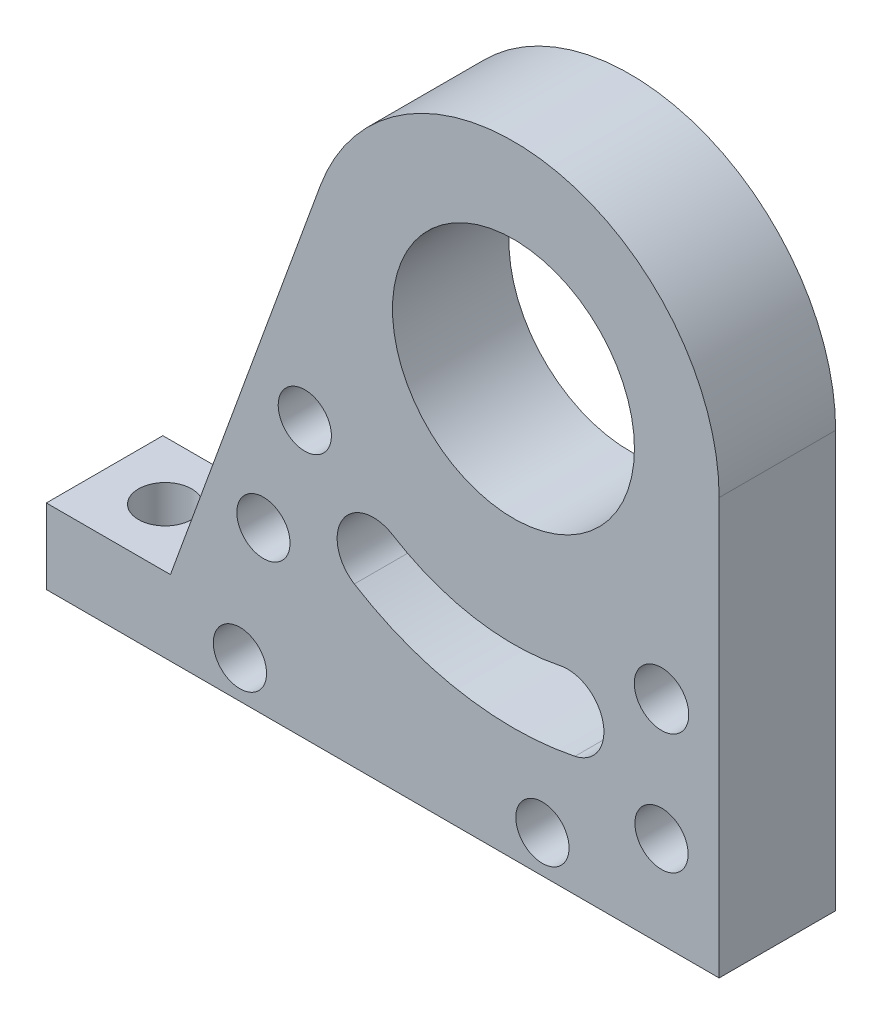
SolidWorks part; units mm, degrees
material "6061 Alloy"
ref_plane "Front Plane" through (0, 0, 0) normal (0, 0, 1) x (1, 0, 0)
ref_plane "Top Plane" through (0, 0, 0) normal (0, 1, 0) x (1, 0, 0)
ref_plane "Right Plane" through (0, 0, 0) normal (1, 0, 0) x (0, 0, -1)
sketch "Sketch1" plane through (0, 0, 0) normal (0, 0, 1) x (1, 0, 0)
  line L0 (-26.7836, -11.003) -> (22.5905, -28.9737) construction
  line L1 (0, 0) -> (17.7131, 0) construction
  line L2 (17, 0) -> (17, -34.3882)
  line L3 (-15.9748, 5.8143) -> (-30.6073, -34.3882)
  line L4 (17, -34.3882) -> (-30.6073, -34.3882)
  circle A0 centre (0, 0) radius 10
  arc A1 (-15.9748, 5.8143) -> (17, 0) centre (0, 0) cw
  dimension "D1" = 20
  dimension "D4" = 7
  dimension "D2" = 20
  dimension "D3" = 19.5
  dimension "D5" = 7
extrude "3/8" add sketch "Sketch1" along normal blind 9.63
sketch "Sketch2" plane through (0, 0, 0) normal (0, 0, 1) x (1, 0, 0)
  line L2 (12.2375, -26.8001) -> (12.2375, -16.8001) construction
  line L4 (-20.6657, -20.9984) -> (-17.2455, -11.6014) construction
  line L5 (-15.9748, 5.8143) -> (-30.6073, -34.3882) construction
  line L6 (17, 0) -> (17, -34.3882) construction
  circle A0 centre (12.2375, -26.8001) radius 2.2
  circle A1 centre (12.2375, -16.8001) radius 2.25
  circle A2 centre (-20.6657, -20.9984) radius 2.2
  circle A3 centre (-17.2455, -11.6014) radius 2.2
  arc A4 (-18.9556, -16.2999) -> (12.2375, -21.8001) centre (0, 0) ccw construction
  dimension "D3" = 4.4
  dimension "D6" = 4.4
  dimension "D7" = 25
  dimension "D1" = 4.7625
  dimension "D2" = 10
  dimension "D4" = 10
  dimension "D5" = 4.7625
extrude "M4_through" cut sketch "Sketch2" along normal up to surface (9.63 mm away) up to face at (-2.5357, -12.2819, 9.63)
sketch "Sketch4" plane through (0, 0, 9.63) normal (0, 0, 1) x (1, 0, 0)
  line L0 (-15.9748, 5.8143) -> (-30.6073, -34.3882) construction
  line L1 (17, -34.3882) -> (17, 0) construction
  arc A0 (-11.5723, -18.7105) -> (4.475, -21.5401) centre (0, 0) ccw construction
  arc A1 (-9.9942, -16.1591) -> (3.8648, -18.6028) centre (0, 0) ccw
  arc A2 (-13.1503, -21.2619) -> (5.0852, -24.4773) centre (0, 0) ccw
  arc A3 (-9.9942, -16.1591) -> (-13.1503, -21.2619) centre (-11.5723, -18.7105) ccw
  arc A4 (3.8648, -18.6028) -> (5.0852, -24.4773) centre (4.475, -21.5401) cw
  dimension "D1" = 22
  dimension "D2" = 6
  dimension "D3" = 3
  dimension "D4" = 12.525
  dimension "D5" = 12.525
extrude "Cut-Extrude2" cut sketch "Sketch4" against normal up to surface (9.63 mm away) up to face at (14.4375, -26.8001, 0)
sketch "Sketch6" plane through (0, 0, 9.63) normal (0, 0, 1) x (1, 0, 0)
  line L0 (-30.6073, -34.3882) -> (-38.6073, -34.3882)
  line L1 (-38.6073, -34.3882) -> (-38.6073, -28.1882)
  line L2 (-38.6073, -28.1882) -> (-28.3507, -28.1882)
  line L3 (-15.9748, 5.8143) -> (-30.6073, -34.3882) construction
  line L4 (-28.3507, -28.1882) -> (-30.6073, -34.3882)
  dimension "D1" = 8
  dimension "D2" = 6.2
extrude "Boss-Extrude2" add sketch "Sketch6" against normal up to surface (9.63 mm away) up to face at (-3.588, -20.3485, 0)
sketch "Sketch5" plane through (0, -34.3882, 0) normal (0, -1, 0) x (1, 0, 0)
  line L0 (-38.6073, 4.815) -> (17, 4.815) construction
  line L2 (17, 9.63) -> (17, 0) construction
  line L3 (-38.6073, 0) -> (-38.6073, 9.63) construction
  circle A0 centre (-33.6073, 4.815) radius 2.2
  circle A1 centre (-8.6073, 4.815) radius 2.2
  dimension "D1" = 4.4
  dimension "D2" = 4.4
  dimension "D3" = 5
  dimension "D4" = 25
extrude "M5_DRILL" cut sketch "Sketch5" against normal blind 8
sketch "Sketch7" plane through (0, 0, 9.63) normal (0, 0, 1) x (1, 0, 0)
  line L0 (-38.6073, -31.2882) -> (-22.6073, -31.2882) construction
  line L1 (-38.6073, -28.1882) -> (-38.6073, -34.3882) construction
  circle A0 centre (-22.6073, -31.2882) radius 2.2
  circle A1 centre (2.3927, -31.2882) radius 2.2
  dimension "D1" = 4.4
  dimension "D3" = 2
  dimension "D2" = 16
extrude "M4_through2" cut sketch "Sketch7" against normal up to surface (9.63 mm away) up to face at (-3.588, -20.3485, 0)
